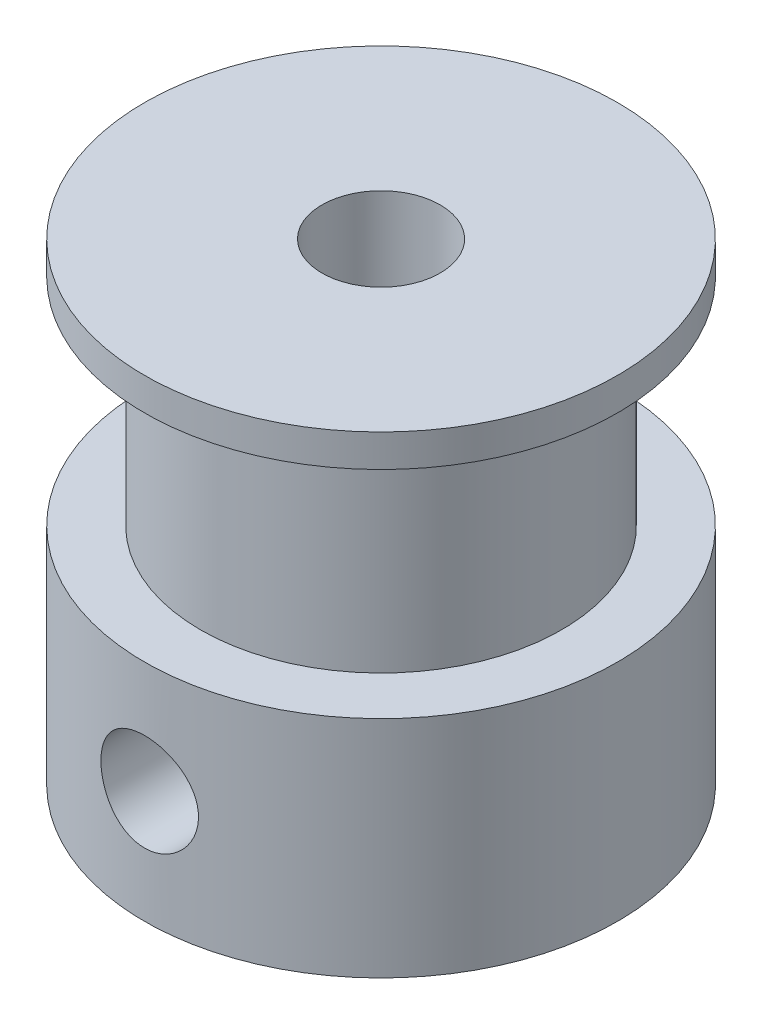
SolidWorks part; units mm, degrees
ref_plane "Plan de face" through (0, 0, 0) normal (0, 0, 1) x (1, 0, 0)
ref_plane "Plan de dessus" through (0, 0, 0) normal (0, 1, 0) x (1, 0, 0)
ref_plane "Plan de droite" through (0, 0, 0) normal (1, 0, 0) x (0, 0, -1)
sketch "Esquisse2" plane through (0, 0, 0) normal (0, 0, 1) x (1, 0, 0)
  line L1 (2, 16) -> (8, 16)
  line L2 (8, 16) -> (8, 14.9)
  line L3 (8, 14.9) -> (6.11, 14.9)
  line L4 (6.11, 14.9) -> (6.11, 7.6)
  line L5 (6.11, 7.6) -> (8, 7.6)
  line L6 (8, 7.6) -> (8, 0)
  line L7 (8, 0) -> (2, 0)
  line L8 (0, 0) -> (0, 29.6666) construction
  line L9 (2, 0) -> (2, 16)
  dimension "D1" = 4
  dimension "D2" = 16
  dimension "D3" = 16
  dimension "D4" = 7.3
  dimension "D5" = 12.22
  dimension "D6" = 1.1
revolve "Révolution1" add sketch "Esquisse2" angle 360 about L8
ref_axis "Axe1" through (0, 16, 0) along (0, -1, 0)
hole_wizard "Trou pour taraudage pour trou taraudé M41" positions "Esquisse3" profile "Esquisse4" hole size "M4" standard "ISO" end condition through all
sketch "Esquisse3" plane through (0, 0, 0) normal (0, 0, 1) x (1, 0, 0)
  line L0 (0, 7.6) -> (0, 0) construction
  line L1 (8, 7.6) -> (-8, 7.6) construction
  point P0 (0, 3.8)
sketch "Esquisse4" plane through (0, 3.8, 0) normal (1, 0, 0) x (0, 1, 0)
  line L0 (0, 0) -> (0, 8)
  line L1 (0, 8) -> (1.65, 8)
  line L2 (1.65, 8) -> (1.65, 0)
  line L5 (1.65, 0) -> (0, 0)
  line L11 (0, -6.35) -> (0, 107.95) construction
  dimension "Diamètre du perçage jusqu'au prochain" = 3.3
  dimension "Profondeur du perçage jusqu'au prochain" = 8
ref_plane "Plan1" through (0, 11.25, 0) normal (0, -1, 0) x (-1, 0, 0)
pattern_circular "Répétition circulaire1" count 2 every 90 about axis through (0, 16, 0) along (0, -1, 0) of "Trou pour taraudage pour trou taraudé M41"
